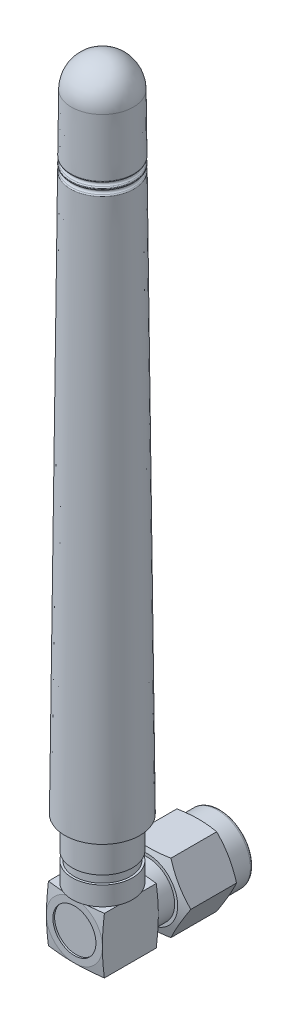
SolidWorks part; units mm, degrees
ref_plane "Спереди" through (0, 0, 0) normal (0, 0, 1) x (1, 0, 0)
ref_plane "Сверху" through (0, 0, 0) normal (0, 1, 0) x (1, 0, 0)
ref_plane "Справа" through (0, 0, 0) normal (1, 0, 0) x (0, 0, -1)
sketch "Эскиз1" plane through (0, 0, 0) normal (0, 0, 1) x (1, 0, 0)
  line L1 (-3.25, -3.25) -> (3.25, -3.25)
  line L2 (-3.25, -3.25) -> (-3.25, 3.25)
  line L3 (-3.25, 3.25) -> (3.25, 3.25)
  line L4 (3.25, -3.25) -> (3.25, 3.25)
  line L5 (-3.25, -3.25) -> (3.25, 3.25) construction
  line L6 (-3.25, 3.25) -> (3.25, -3.25) construction
  point P0 (0, 0)
  dimension "D1" = 6.5
  dimension "D2" = 6.5
extrude "Бобышка-Вытянуть1" add sketch "Эскиз1" along normal mid plane 6.5
sketch "Эскиз2" plane through (0, 0, 3.25) normal (0, 0, 1) x (1, 0, 0)
  circle A0 centre (0, 0) radius 3.26
  dimension "D1" = 6.52
extrude "Вырез-Вытянуть1" cut sketch "Эскиз2" against normal blind 6.5 draft 80 flip side to cut
mirror "Зеркальное отражение1" about plane through (0, 0, 0) normal (0, 0, 1) of "Вырез-Вытянуть1"
sketch "Эскиз3" plane through (0, 0, 3.25) normal (0, 0, 1) x (1, 0, 0)
  circle A0 centre (0, 0) radius 2.5
  dimension "D1" = 5
extrude "Вырез-Вытянуть2" cut sketch "Эскиз3" against normal blind 0.2
sketch "Эскиз4" plane through (0, 0, -3.25) normal (0, 0, -1) x (-1, 0, 0)
  circle A0 centre (0, 0) radius 3.15
  dimension "D1" = 6.3
extrude "Бобышка-Вытянуть2" add sketch "Эскиз4" along normal blind 2
sketch "Эскиз5" plane through (0, 0, -5.25) normal (0, 0, -1) x (-1, 0, 0)
  line L1 (4.6188, 0) -> (2.3094, 4)
  line L2 (2.3094, 4) -> (-2.3094, 4)
  line L3 (-2.3094, 4) -> (-4.6188, 0)
  line L4 (-4.6188, 0) -> (-2.3094, -4)
  line L5 (-2.3094, -4) -> (2.3094, -4)
  line L6 (2.3094, -4) -> (4.6188, 0)
  circle A0 centre (0, 0) radius 4 construction
  dimension "D1" = 8
extrude "Бобышка-Вытянуть3" add sketch "Эскиз5" along normal blind 6
sketch "Эскиз6" plane through (0, 0, -5.25) normal (0, 0, 1) x (1, 0, 0)
  circle A0 centre (0, 0) radius 3.5
  circle A1 centre (0, 0) radius 10
  dimension "D1" = 7
  dimension "D2" = 20
extrude "Вырез-Вытянуть3" cut sketch "Эскиз6" against normal blind 6 draft 70
sketch "Эскиз7" plane through (0, 0, -11.25) normal (0, 0, -1) x (-1, 0, 0)
  circle A0 centre (0, 0) radius 3.85
  dimension "D1" = 7.7
extrude "Бобышка-Вытянуть4" add sketch "Эскиз7" along normal offset from surface (2.45 mm away) 8.45 up to face at (-3.15, 0, -5.25)
sketch "Эскиз8" plane through (0, 0, -11.25) normal (0, 0, -1) x (-1, 0, 0)
  circle A0 centre (0, 0) radius 3.85 construction
  circle A1 centre (0, 0) radius 3.85
  circle A2 centre (0, 0) radius 10 construction
  dimension "D1" = 20
extrude "Вырез-Вытянуть6" cut sketch "Эскиз8" against normal blind 6 draft 70 flip side to cut
sketch "Эскиз9" plane through (0, 0, -13.7) normal (0, 0, -1) x (-1, 0, 0)
  circle A0 centre (0, 0) radius 2.815
  dimension "D1" = 5.63
extrude "Вырез-Вытянуть7" cut sketch "Эскиз9" against normal blind 3.2
fillet "Скругление1" radius 0.35 1 edges at (-3.85, 0, -13.7)
chamfer "Фаска1" distance 0.35 angle 45 1 edges at (-2.815, 0, -13.7)
sketch "Эскиз10" plane through (0, 0, -10.5) normal (0, 0, -1) x (-1, 0, 0)
  circle A0 centre (0, 0) radius 2.615
  circle A1 centre (0, 0) radius 2.815
  circle A2 centre (0, 0) radius 2.815
  dimension "D1" = 0
  dimension "D2" = 0.2
extrude "Вырез-Вытянуть8" cut sketch "Эскиз10" against normal blind 2
sketch "Эскиз11" plane through (0, 0, -10.5) normal (0, 0, -1) x (-1, 0, 0)
  circle A0 centre (0, 0) radius 0.325
  dimension "D1" = 0.65
extrude "Бобышка-Вытянуть5" add sketch "Эскиз11" along normal blind 2.5
chamfer "Фаска2" distance 0.3 angle 45 1 edges at (-0.325, 0, -13)
sketch "Эскиз12" plane through (0, 0, 0) normal (1, 0, 0) x (0, 0, -1)
  line L0 (0, 0) -> (0, 94.8363) construction
  line L1 (0, 3.25) -> (3.5, 3.25)
  line L2 (-3.0144, 3.25) -> (3.0144, 3.25) construction
  line L3 (3.5, 3.25) -> (3.5, 5.45)
  line L4 (3.5, 10.45) -> (4.35, 10.45)
  line L5 (4.35, 10.45) -> (3.6846, 74.8292)
  line L6 (-3.0144, -3.25) -> (3.0144, -3.25) construction
  line L7 (3.6687, 76.3708) -> (3.5998, 83.0372)
  line L8 (3.677, 75.5708) -> (3.6764, 75.6292)
  line L9 (3.5, 6.45) -> (3.5, 10.45)
  line L10 (3.5, 5.45) -> (3.25, 5.45)
  line L12 (3.5, 6.45) -> (3.25, 6.45)
  line L13 (3.25, 5.45) -> (3.25, 6.45)
  line L14 (3.75, 5.45) -> (3.25, 6.45) construction
  line L15 (3.75, 6.45) -> (3.25, 5.45) construction
  line L16 (0, 3.25) -> (0, 86.6)
  arc A0 (3.5998, 83.0372) -> (0, 86.6) centre (0, 83) ccw
  arc A1 (3.5764, 76.2308) -> (3.5812, 75.7673) centre (3.6725, 76) ccw
  arc A2 (3.5847, 75.4308) -> (3.5895, 74.9673) centre (3.6808, 75.2) ccw
  arc A3 (3.5812, 75.7673) -> (3.6764, 75.6292) centre (3.5264, 75.6277) cw
  arc A4 (3.5847, 75.4308) -> (3.677, 75.5708) centre (3.527, 75.5692) ccw
  arc A5 (3.5764, 76.2308) -> (3.6687, 76.3708) centre (3.5187, 76.3692) ccw
  arc A6 (3.5895, 74.9673) -> (3.6846, 74.8292) centre (3.5346, 74.8277) cw
  point P24 (3.6782, 75.45)
  point P27 (3.67, 76.25)
  point P30 (3.5, 5.95)
  dimension "D1" = 7.2
  dimension "D6" = 0.5
  dimension "D7" = 0.8
  dimension "D9" = 0.15
  dimension "D10" = 0.15
  dimension "D2" = 8.7
  dimension "D3" = 7
  dimension "D4" = 7.2
  dimension "D5" = 89.85
  dimension "D8" = 10.6
  dimension "D11" = 1
  dimension "D12" = 6.5
  dimension "D13" = 4
revolve "Повернуть1" add sketch "Эскиз12" angle 360 about L16
chamfer "Фаска3" distance 0.8 angle 60.5 1 edges at (0, 10.45, -3.5) first distance on face at (0, 10.45, -3.5)
